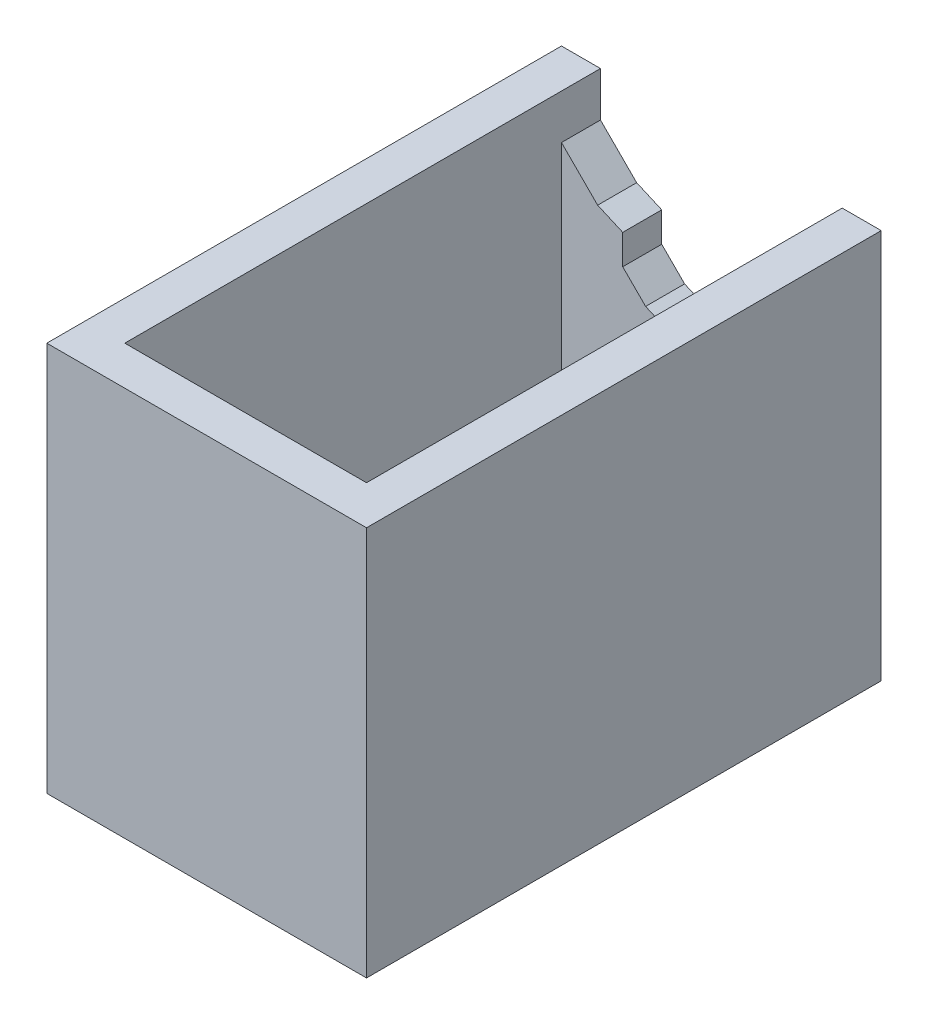
SolidWorks part; units mm, degrees
ref_plane "Front Plane" through (0, 0, 0) normal (0, 0, 1) x (1, 0, 0)
ref_plane "Top Plane" through (0, 0, 0) normal (0, 1, 0) x (1, 0, 0)
ref_plane "Right Plane" through (0, 0, 0) normal (1, 0, 0) x (0, 0, -1)
sketch "Sketch1" plane through (0, 0, 0) normal (0, 1, 0) x (1, 0, 0)
  line L0 (0, 0) -> (0, -2) construction
  line L1 (0, 0) -> (12.4, 0)
  line L2 (0, 0) -> (0, 22.4)
  line L3 (0, 22.4) -> (12.4, 22.4)
  line L4 (12.4, 0) -> (12.4, 22.4)
  line L5 (0, -2) -> (-2, -2) construction
  line L6 (12.4, 22.4) -> (12.4, 24.4) construction
  line L7 (12.4, 24.4) -> (14.4, 24.4) construction
  line L9 (-2, -2) -> (14.4, -2)
  line L10 (-2, -2) -> (-2, 24.4)
  line L11 (-2, 24.4) -> (14.4, 24.4)
  line L12 (14.4, -2) -> (14.4, 24.4)
  dimension "D1" = 22.4
  dimension "D2" = 12.4
  dimension "D3" = 2
  dimension "D4" = 2
  dimension "D5" = 2
  dimension "D6" = 2
extrude "Boss-Extrude1" add sketch "Sketch1" along normal blind 20
sketch "Sketch2" plane through (0, 0, -24.4) normal (0, 0, -1) x (-1, 0, 0)
  line L0 (-12.4, 20) -> (-12.4, 17.7121)
  line L1 (-12.4, 17.7121) -> (-10.5445, 15.8566)
  line L2 (-10.5445, 15.8566) -> (-9.2581, 15.2935)
  line L3 (-9.2581, 15.2935) -> (-9.2581, 13.7641)
  line L4 (-9.2581, 13.7641) -> (-8.0844, 12.5904)
  line L5 (-8.0844, 12.5904) -> (-6.2, 11.7656)
  line L6 (-6.2, 11.7656) -> (-6.2, 17.9966) construction
  line L7 (-4.3156, 12.5904) -> (-6.2, 11.7656)
  line L8 (-3.1419, 13.7641) -> (-4.3156, 12.5904)
  line L9 (-3.1419, 15.2935) -> (-3.1419, 13.7641)
  line L10 (-1.8555, 15.8566) -> (-3.1419, 15.2935)
  line L11 (0, 17.7121) -> (-1.8555, 15.8566)
  line L12 (0, 20) -> (0, 17.7121)
  line L13 (-12.4, 20) -> (0, 20)
extrude "Cut-Extrude1" cut sketch "Sketch2" against normal blind 10
ref_plane "Plane2" through (0, 30, 0) normal (0, 1, 0) x (1, 0, 0)
sketch "Sketch4" plane through (0, 30, 0) normal (0, 1, 0) x (1, 0, 0)
  line L0 (12.4, 0) -> (12.4, 24.4) construction
  line L1 (12.4, 12.2) -> (14.4, 12.2)
  line L2 (12.4, 12.2) -> (12.4, 22.7975)
  line L3 (12.3727, 36.9975) -> (14.4, 36.9975)
  line L4 (14.4, 12.2) -> (14.4, 36.9975)
  line L5 (7.8651, 36.9975) -> (7.8651, 34.9975) construction
  line L6 (12.3727, 36.9975) -> (7.8651, 36.9975)
  line L7 (12.0651, 25.7975) -> (10.0651, 25.7975)
  line L8 (12.0651, 34.9975) -> (7.8651, 34.9975)
  line L9 (12.0651, 34.9975) -> (12.0651, 25.7975)
  line L10 (7.8651, 36.9975) -> (5.8651, 36.9975)
  line L11 (7.8651, 34.9975) -> (7.8651, 32.4736)
  line L12 (7.8651, 32.4736) -> (5.8651, 32.4736)
  line L13 (5.8651, 36.9975) -> (5.8651, 32.4736)
  line L14 (10.0651, 25.7975) -> (10.0651, 26.7975)
  line L15 (10.0651, 26.7975) -> (9.0651, 26.7975)
  line L16 (9.0651, 26.7975) -> (9.0651, 26.9676)
  line L17 (9.0651, 26.9676) -> (9.0651, 22.7975)
  line L18 (9.0651, 22.7975) -> (12.4, 22.7975)
  line L19 (10.0651, 25.7975) -> (10.0651, 22.7975) construction
  line L20 (11.9651, 34.8975) -> (12.0651, 34.8975) construction
  line L21 (10.0651, 26.7975) -> (10.0651, 26.8975) construction
  line L22 (11.9651, 26.8975) -> (8.9651, 26.8975) construction
  line L23 (11.9651, 34.8975) -> (11.9651, 34.9975) construction
  dimension "D1" = 2
  dimension "D2" = 2
  dimension "D3" = 2
  dimension "D4" = 1
  dimension "D5" = 1
  dimension "D6" = 2
  dimension "D7" = 3
  dimension "D8" = 4.2
  dimension "D9" = 0.1
  dimension "D10" = 0.1
  dimension "D11" = 0.1
